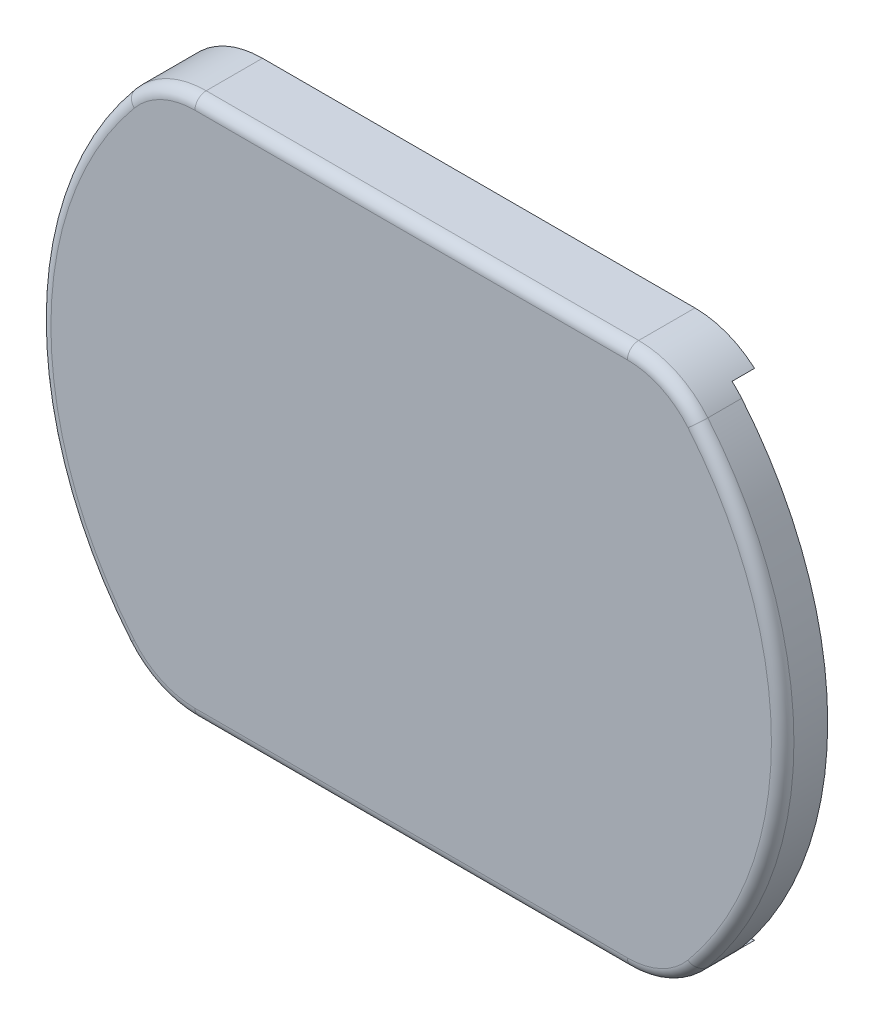
SolidWorks part; units mm, degrees
ref_plane "Front Plane" through (0, 0, 0) normal (0, 0, 1) x (1, 0, 0)
ref_plane "Top Plane" through (0, 0, 0) normal (0, 1, 0) x (1, 0, 0)
ref_plane "Right Plane" through (0, 0, 0) normal (1, 0, 0) x (0, 0, -1)
sketch "Sketch1" plane through (0, 0, 0) normal (0, 0, 1) x (1, 0, 0)
  line L0 (0, 12) -> (0, -12) construction
  line L4 (-9.6047, -12) -> (9.6047, -12)
  line L5 (9.6047, 12) -> (-9.6047, 12)
  arc A13 (-12.6782, -10.56) -> (-9.6047, -12) centre (-9.6047, -8) ccw
  arc A14 (9.6047, -12) -> (12.6782, -10.56) centre (9.6047, -8) ccw
  arc A15 (-12.6782, 10.56) -> (-12.6782, -10.56) centre (0, 0) ccw
  arc A16 (-9.6047, 12) -> (-12.6782, 10.56) centre (-9.6047, 8) ccw
  arc A17 (12.6782, -10.56) -> (12.6782, 10.56) centre (0, 0) ccw
  arc A18 (12.6782, 10.56) -> (9.6047, 12) centre (9.6047, 8) ccw
  point P13 (8.3983, 17.228)
  point P16 (-11.3248, -12)
  point P18 (11.3248, -12)
  point P19 (11.3248, 12)
  point P20 (-11.3248, 12)
  dimension "D1" = 24
  dimension "D2" = 4
  dimension "D3" = 16.5
  dimension "D4" = 22.6495
extrude "Extrude1" add sketch "Sketch1" along normal blind 3
fillet "Fillet2" radius 0.5 8 edges at (-16.5, 0, 3) (-11.3017, 11.6222, 3) (0, 12, 3) (11.3017, 11.6222, 3) (16.5, 0, 3) (11.3017, -11.6222, 3) (0, -12, 3) (-11.3017, -11.6222, 3)
sketch "Sketch4" plane through (0, 0, 0) normal (1, 0, 0) x (0, 0, -1)
  line L1 (-0.75, 10.5) -> (-0.75, 11)
  line L3 (-0.75, 11) -> (-1, 11)
  line L5 (-1, 10.5) -> (-1, 11)
  line L6 (-0.75, 10.5) -> (-1, 10.5)
sketch "Sketch2" plane through (0, 0, 0) normal (0, 0, -1) x (-1, 0, 0)
  line L2 (9.6047, 10.5) -> (-12.7279, 10.5)
  line L3 (9.6047, -10.5) -> (-12.7279, -10.5)
  arc A0 (-12.6782, 10.56) -> (-12.6782, -10.56) centre (0, 0) ccw construction
  arc A1 (-12.7279, 10.5) -> (-12.7279, -10.5) centre (0, 0) ccw
  arc A9 (9.6047, -10.5) -> (11.5256, -9.6) centre (9.6047, -8) ccw
  arc A10 (11.5256, 9.6) -> (9.6047, 10.5) centre (9.6047, 8) ccw
  arc A11 (11.5256, -9.6) -> (11.5256, 9.6) centre (0, 0) ccw
  arc A12 (9.6047, -10.5) -> (11.5256, -9.6) centre (9.6047, -8) ccw
  arc A13 (11.5256, 9.6) -> (9.6047, 10.5) centre (9.6047, 8) ccw
  arc A14 (11.5256, -9.6) -> (11.5256, 9.6) centre (0, 0) ccw
  dimension "D1" = 1.5
extrude "Cut-Extrude1" cut sketch "Sketch2" against normal up to vertex (1 mm away) up to point (0, 10.5, 1)
sketch "d1mm" plane through (0, 0, 0) normal (0, 0, -1) x (-1, 0, 0)
  line L2 (-10.5, -11) -> (-10.5, 11)
  line L3 (-10.5, 11) -> (-12.2984, 11)
  line L5 (-12.2984, -11) -> (-10.5, -11)
  arc A1 (-12.2984, 11) -> (-12.2984, -11) centre (0, 0) ccw
extrude "Cut-Extrude2" cut sketch "d1mm" against normal up to surface (1 mm away) up to face at (-2.7846, 0, 1)
sketch "Sketch5" plane through (10.5, 0, 0) normal (1, 0, 0) x (0, 0, -1)
  line L4 (-0.75, 10.5) -> (-0.75, 11)
  line L5 (-0.75, 11) -> (-1, 11)
  line L6 (-1, 11) -> (-1, 10.5)
  line L7 (-1, 10.5) -> (-0.75, 10.5)
  line L8 (-0.75, 10.5) -> (-0.75, 11)
  line L9 (-0.75, 11) -> (-1, 11)
  line L10 (-1, 11) -> (-1, 10.5)
  line L11 (-1, 10.5) -> (-0.75, 10.5)
  dimension "D1" = 0
extrude "Cut-Extrude5" cut sketch "Sketch5" against normal blind 20
mirror "Mirror3" about plane through (0, 0, 0) normal (0, 1, 0) of "Cut-Extrude5"
